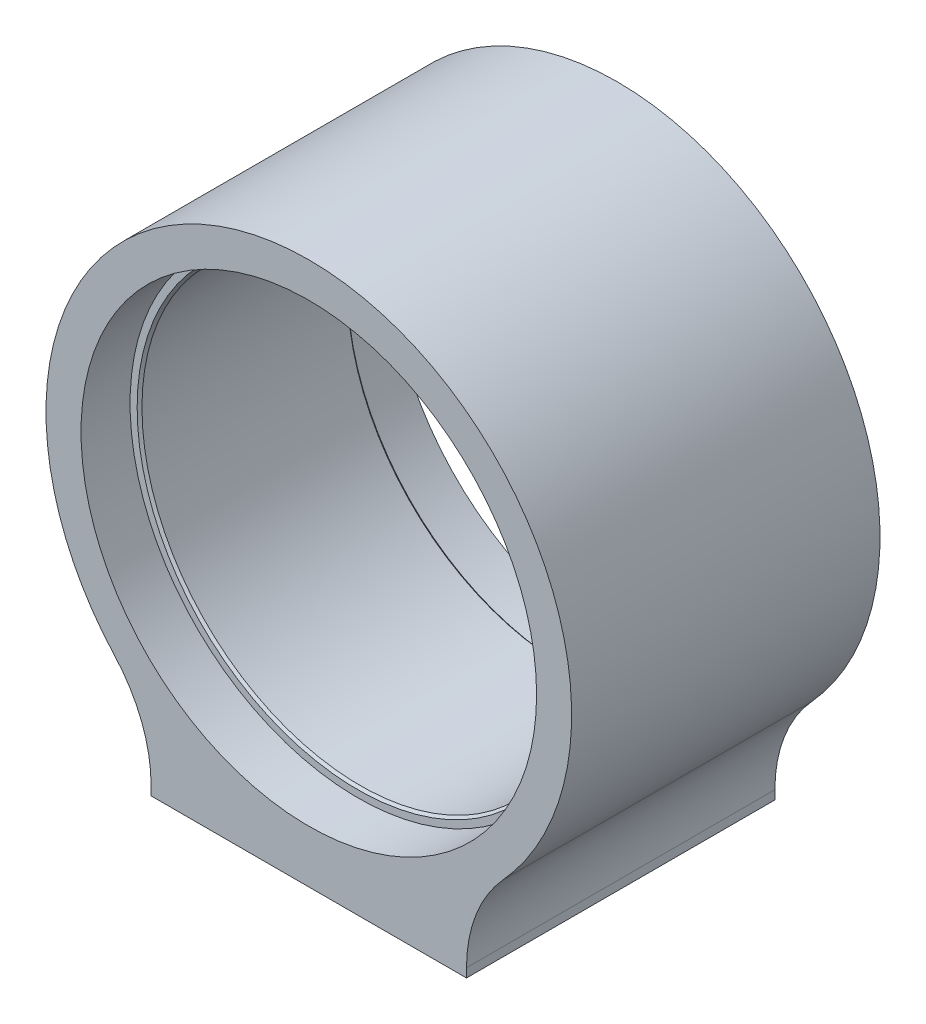
SolidWorks part; units mm, degrees
ref_plane "Front Plane" through (0, 0, 0) normal (0, 0, 1) x (1, 0, 0)
ref_plane "Top Plane" through (0, 0, 0) normal (0, 1, 0) x (1, 0, 0)
ref_plane "Right Plane" through (0, 0, 0) normal (1, 0, 0) x (0, 0, -1)
ref_plane "Plane1"
sketch "Sketch1" plane through (0, 0, 0) normal (0, 0, 1) x (1, 0, 0)
  circle A0 centre (0, 0) radius 37.5
  circle A1 centre (0, 0) radius 31.15
  circle A2 centre (31.65, 0) radius 1.5
  circle A3 centre (30.7969, 7.299) radius 1.5
  circle A4 centre (28.2835, 14.2045) radius 1.5
  circle A5 centre (24.2453, 20.3442) radius 1.5
  circle A6 centre (18.9001, 25.3872) radius 1.5
  circle A7 centre (12.5359, 29.0615) radius 1.5
  circle A8 centre (5.496, 31.1692) radius 1.5
  circle A9 centre (-1.8403, 31.5965) radius 1.5
  circle A10 centre (-9.0773, 30.3204) radius 1.5
  circle A11 centre (-15.825, 27.4097) radius 1.5
  circle A12 centre (-21.7195, 23.0214) radius 1.5
  circle A13 centre (-26.4432, 17.392) radius 1.5
  circle A14 centre (-29.7413, 10.8249) radius 1.5
  circle A15 centre (-31.436, 3.6743) radius 1.5
  circle A16 centre (-31.436, -3.6743) radius 1.5
  circle A17 centre (-29.7413, -10.8249) radius 1.5
  circle A18 centre (-26.4432, -17.392) radius 1.5
  circle A19 centre (-21.7195, -23.0214) radius 1.5
  circle A20 centre (-15.825, -27.4097) radius 1.5
  circle A21 centre (-9.0773, -30.3204) radius 1.5
  circle A22 centre (-1.8403, -31.5965) radius 1.5
  circle A23 centre (5.496, -31.1692) radius 1.5
  circle A24 centre (12.5359, -29.0615) radius 1.5
  circle A25 centre (18.9001, -25.3872) radius 1.5
  circle A26 centre (24.2453, -20.3442) radius 1.5
  circle A27 centre (28.2835, -14.2045) radius 1.5
  circle A28 centre (30.7969, -7.299) radius 1.5
  dimension "D1" = 75
  dimension "D3" = 3
  dimension "D4" = 62.3
  dimension "D2" = 31.65
extrude "Extrusion1" add sketch "Sketch1" along normal blind 15 and the other way blind 15 contours A1 A2 | A1 A3 | A1 A4 | A1 A5 | A1 A6 | A1 A7 | A1 A8 | A1 A9 | A1 A10 | A1 A11 | A1 A12 | A1 A13 | A1 A14 | A1 A15 | A1 A16 | A1 A17 | A1 A18 | A1 A19 | A1 A20 | A1 A21 | A1 A22 | A1 A23 | A1 A24 | A1 A25 | A1 A26 | A1 A27 | A1 A28 | A0 A28 A1 A27 A26 A25 A24 A23 A22 A21 A20 A19 A18 A17 A16 A15 A14 A13 A12 A11 A10 A9 A8 A7 A6 A5 A4 region at (-36.4393, 0, 0) region at (32.0214, 0, 0) region at (31.1583, 7.3846, 0) region at (31.1583, -7.3846, 0) region at (28.6154, 14.3712, 0) region at (28.6154, -14.3712, 0) region at (24.5298, 20.583, 0) region at (24.5298, -20.583, 0) region at (19.1219, 25.6851, 0) region at (19.1219, -25.6851, 0) region at (12.683, 29.4026, 0) region at (12.683, -29.4026, 0) region at (5.5605, 31.5349, 0) region at (5.5605, -31.5349, 0) region at (-1.8619, 31.9672, 0) region at (-1.8619, -31.9672, 0) region at (-9.1838, 30.6762, 0) region at (-9.1838, -30.6762, 0) region at (-16.0107, 27.7314, 0) region at (-16.0107, -27.7314, 0) region at (-21.9744, 23.2915, 0) region at (-21.9744, -23.2915, 0) region at (-26.7535, 17.5961, 0) region at (-26.7535, -17.5961, 0) region at (-30.0903, 10.952, 0) region at (-30.0903, -10.952, 0) region at (-31.8049, 3.7175, 0) region at (-31.8049, -3.7175, 0)
ref_plane "Plane2" through (0, 0, 15) normal (0, 0, 1) x (1, 0, 0)
sketch "Sketch2" plane through (0, 0, 15) normal (0, 0, 1) x (1, 0, 0)
  arc A0 (30.8923, 2.8215) -> (30.7102, 4.3788) centre (-1.6683, -0.195) ccw
  arc A1 (30.7102, 4.3788) -> (30.8923, 2.8215) centre (28.6751, 3.3516) ccw
  circle A2 centre (0, 0) radius 31.15 construction
  dimension "D1" = 32.7
extrude "Extrusion3" sketch "Sketch2" rebuild error yes
ref_plane "Plane3" through (0, 0, 0) normal (-1, 0, 0) x (0, 0, 1)
ref_plane "Plane4" through (0, 0, 0) normal (0, -1, 0) x (0, 0, 1)
ref_axis "Axis1" through (0, 0, 80.9) along (0, 0, -1)
pattern_circular "CirPattern1" count 27 every 13.333 about axis through (0, 0, 80.9) along (0, 0, -1) rebuild error yes
hole_wizard "Hole4" positions "Sketch4" profile "Sketch3" legacy
sketch "Sketch4" plane through (0, 0, 15) normal (0, 0, 1) x (1, 0, 0)
  point P1 (35, 0)
  point P2 (13.8628, 32.1376)
  point P3 (-24.0185, 25.4581)
  point P4 (-32.8892, -11.9707)
  point P5 (-2.0351, -34.9408)
  point P6 (31.2771, -15.708)
sketch "Sketch3" plane through (35, 0, 15) normal (1, 0, 0) x (0, -1, 0)
  line L0 (0, 0) -> (0, 9.25)
  line L1 (0, 9.25) -> (1.25, 8)
  line L2 (1.25, 8) -> (1.25, 0)
  line L4 (1.25, 0) -> (0, 0)
  line L6 (0, 9.25) -> (-1.25, 8) construction
  line L7 (0, -4.2442) -> (0, 117.3081) construction
  dimension "Diameter" = 2.5
  dimension "Depth" = 8
  dimension "Drill Angle" = 90
ref_plane "Plane5" through (0, 0, -15) normal (0, 0, -1) x (-1, 0, 0)
sketch "Sketch5" plane through (0, 0, -15) normal (0, 0, -1) x (-1, 0, 0)
  circle A0 centre (0, 0) radius 37.5
  circle A1 centre (0, 0) radius 32.5
  dimension "D1" = 65
extrude "Extrusion11" add sketch "Sketch5" along normal blind 7 contours A0 A1 region at (36.4393, 0, -15)
ref_plane "Plane6" through (0, 0, 15) normal (0, 0, 1) x (1, 0, 0)
sketch "Sketch6" plane through (0, 0, 15) normal (0, 0, 1) x (1, 0, 0)
  circle A0 centre (0, 0) radius 37.5
  circle A1 centre (0, 0) radius 32.5
  dimension "D1" = 65
extrude "Extrusion17" add sketch "Sketch6" along normal blind 7 contours A0 A1 region at (-36.4393, 0, 15)
ref_plane "Plane7" through (0, 0, 0) normal (0, 0, 1) x (1, 0, 0)
sketch "Sketch7" plane through (0, 0, 0) normal (0, 0, 1) x (1, 0, 0)
  line L0 (22.5, -40) -> (-22.5, -40)
  line L1 (-22.5, -40) -> (-22.5, -30)
  line L2 (22.5, -30) -> (22.5, -40)
  arc A0 (-22.5, -30) -> (22.5, -30) centre (0, 0) ccw
  dimension "D1" = 45
extrude "Extrusion18" add sketch "Sketch7" along normal up to surface and the other way up to surface up to face at (32.5, 0, 22) other way up to face at (-32.5, 0, -22)
fillet "Fillet5" radius 20 2 edges at (22.5, -30, 0) (-22.5, -30, 0)
ref_plane "Plane8" through (0, 0, 0) normal (1, 0, 0) x (0, 1, 0)
sketch "Sketch8" plane through (0, 0, 0) normal (1, 0, 0) x (0, 1, 0)
  line L0 (31.493, 15) -> (30.493, 15)
  line L1 (30.493, 15) -> (30.493, 14)
  line L2 (30.493, 14) -> (31.493, 15)
  line L3 (0, 0) -> (0, 29.5496) construction
  dimension "D1" = 1
  dimension "D2" = 135
revolve "Revolution1" cut sketch "Sketch8" angle 360 about L3
ref_plane "Plane9" through (0, 0, 0) normal (0, 0, 1) x (1, 0, 0)
mirror "Mirror1" about plane through (0, 0, 0) normal (0, 0, 1) of "Revolution1"
hole_wizard "Hole6" positions "Sketch10" profile "Sketch9" legacy
sketch "Sketch10" plane through (0, -40, 0) normal (0, -1, 0) x (-1, 0, 0)
  point P1 (-17.5, -17.5)
  point P2 (-17.5, 17.5)
  point P3 (17.5, -17.5)
  point P4 (17.5, 17.5)
sketch "Sketch9" plane through (17.5, -40, 17.5) normal (1, 0, 0) x (0, 0, -1)
  line L0 (0, 0) -> (0, 8.7511)
  line L1 (0, 8.7511) -> (1.25, 8)
  line L2 (1.25, 8) -> (1.25, 0)
  line L4 (1.25, 0) -> (0, 0)
  line L6 (0, 8.7511) -> (-1.25, 8) construction
  line L7 (0, -4.2442) -> (0, 117.3081) construction
  dimension "Diameter" = 2.5
  dimension "Depth" = 8
  dimension "Drill Angle" = 118
